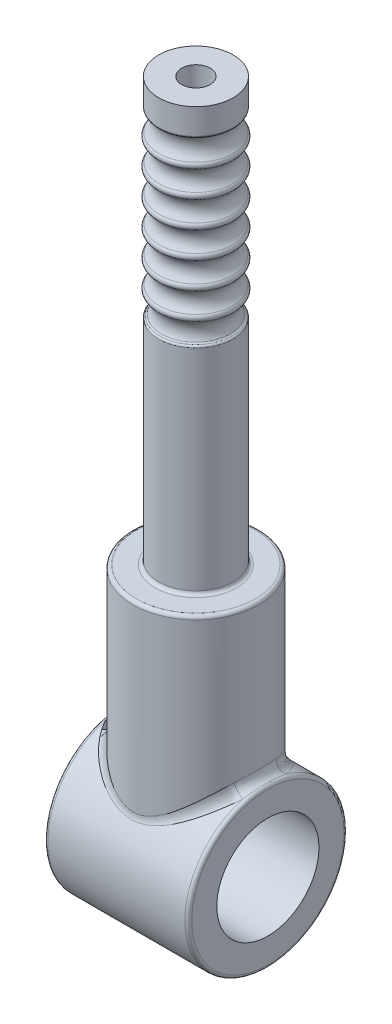
SolidWorks part; units mm, degrees
material "1060 Alloy"
ref_plane "Front Plane" through (0, 0, 0) normal (0, 0, 1) x (1, 0, 0)
ref_plane "Top Plane" through (0, 0, 0) normal (0, 1, 0) x (1, 0, 0)
ref_plane "Right Plane" through (0, 0, 0) normal (1, 0, 0) x (0, 0, -1)
sketch "Sketch1" plane through (0, 0, 0) normal (1, 0, 0) x (0, 0, -1)
  circle A0 centre (0, 0) radius 5.725
  circle A1 centre (0, 0) radius 3.675
  dimension "D1" = 11.45
  dimension "D2" = 7.35
extrude "Boss-Extrude1" add sketch "Sketch1" along normal mid plane 10.35
ref_plane "Plane1" through (0, -5.725, 0) normal (0, -1, 0) x (-1, 0, 0)
sketch "Sketch2" plane through (0, -5.725, 0) normal (0, 1, 0) x (1, 0, 0)
  circle A0 centre (0, 0) radius 4.53
  dimension "D1" = 9.06
extrude "Boss-Extrude2" add sketch "Sketch2" along normal blind 22.6
sketch "Sketch4" plane through (0, 16.875, 0) normal (0, 1, 0) x (1, 0, 0)
  circle A0 centre (0, 0) radius 2.675
  dimension "D1" = 5.35
extrude "Boss-Extrude3" add sketch "Sketch4" along normal blind 53 from surface starting at plane "Plane1"
sketch "Sketch3" plane through (5.175, 0, 0) normal (1, 0, 0) x (0, 0, -1)
  line L0 (4.53, -5.725) -> (4.53, -3.5007) construction
  line L1 (-4.53, -3.5007) -> (-4.53, -5.725) construction
  line L2 (0, -5.725) -> (4.53, -5.725) construction
  line L3 (4.53, -5.725) -> (4.53, -3.5007)
  line L4 (-4.53, -3.5007) -> (-4.53, -5.725)
  line L5 (-4.53, -5.725) -> (4.53, -5.725)
  circle A0 centre (0, 0) radius 3.675 construction
  circle A1 centre (0, 0) radius 5.725 construction
  arc A2 (-4.53, -3.5007) -> (4.53, -3.5007) centre (0, 0) ccw
  circle A3 centre (0, 0) radius 3.675
  circle M1 centre (0, 0) radius 5.725
  circle M2 centre (0, 0) radius 3.675
extrude "Cut-Extrude1" cut sketch "Sketch3" against normal through all contours L4 L5 M1 | L5 L3 M1 | M2 region at (5.175, -5.0878, -3.4462) region at (5.175, -5.0878, 3.4462) region at (5.175, 0, 0)
fillet "Fillet2" radius 0.25 2 edges at (-5.175, 0, -5.725) (5.175, 0, -5.725)
fillet "Fillet1" radius 0.7 1 edges at (-0.1545, 3.5041, 4.5274)
fillet "Fillet3" radius 0.25 2 edges at (0, 16.875, 2.675) (0, 16.875, 4.53)
ref_plane "Plane2" through (0, 45.275, 0) normal (0, 1, 0) x (1, 0, 0)
sketch "Sketch8" plane through (0, 45.275, 0) normal (0, 1, 0) x (1, 0, 0)
  circle A0 centre (0, 0) radius 2.675 construction
  circle A1 centre (0, 0) radius 2.675
extrude "Cut-Extrude2" cut sketch "Sketch8" against normal blind 12.88
sketch "Sketch9" plane through (0, 0, 0) normal (0, 0, 1) x (1, 0, 0)
  line L0 (0, 45.275) -> (0, 32.395)
  line L1 (-2.315, 42.635) -> (-2.315, 35.035) construction
  line L2 (-2.315, 35.035) -> (-2.315, 33.1565) construction
  line L3 (-2.675, 45.275) -> (2.675, 45.275) construction
  line L4 (2.675, 32.395) -> (-2.675, 32.395) construction
  line L5 (0, 32.395) -> (-2.75, 32.395)
  line L6 (-2.75, 32.395) -> (-2.75, 45.275) construction
  line L7 (-2.75, 45.275) -> (0, 45.275)
  line L8 (0, 38.835) -> (-2.75, 38.835) construction
  line L9 (-2.75, 43.585) -> (0, 43.585) construction
  line L10 (-2.75, 41.685) -> (0, 41.685) construction
  line L11 (-2.75, 39.785) -> (0, 39.785) construction
  line L12 (-2.75, 37.885) -> (0, 37.885) construction
  line L13 (-2.75, 35.985) -> (0, 35.985) construction
  line L14 (0, 34.085) -> (-2.75, 34.085) construction
  line L15 (-2.45, 43.585) -> (-2.45, 34.085) construction
  line L18 (-2.675, 32.395) -> (-2.675, 17.125) construction
  circle A0 centre (-2.45, 43.585) radius 0.3
  circle A1 centre (-2.45, 41.685) radius 0.3
  circle A2 centre (-2.45, 39.785) radius 0.3
  circle A3 centre (-2.45, 37.885) radius 0.3
  circle A4 centre (-2.45, 35.985) radius 0.3
  circle A5 centre (-2.45, 34.085) radius 0.3
  arc A6 (-2.6575, 43.8017) -> (-2.525, 45.275) centre (-3.4354, 44.6142) ccw
  arc A7 (-2.646, 43.3579) -> (-2.646, 41.9121) centre (-3.2699, 42.635) cw
  arc A8 (-2.646, 41.4579) -> (-2.646, 40.0121) centre (-3.2699, 40.735) cw
  arc A9 (-2.646, 39.5579) -> (-2.646, 38.1121) centre (-3.2699, 38.835) cw
  arc A10 (-2.646, 37.6579) -> (-2.646, 36.2121) centre (-3.2699, 36.935) cw
  arc A11 (-2.646, 35.7579) -> (-2.646, 34.3121) centre (-3.2699, 35.035) cw
  arc A12 (-2.6575, 33.8683) -> (-2.525, 32.395) centre (-3.4354, 33.0558) cw
  dimension "D1" = 2.75
  dimension "D2" = 0.6
  dimension "D4" = 1.9
  dimension "D5" = 0.15
  dimension "D3" = 2.315
revolve "Revolve1" add sketch "Sketch9" angle 360 about L0 region at (-1.1749, 38.835, 0) region at (-2.45, 43.585, 0) region at (-2.45, 34.085, 0) region at (-2.45, 41.685, 0) region at (-2.45, 35.985, 0) region at (-2.45, 39.785, 0) region at (-2.45, 37.885, 0)
fillet "Fillet5" radius 0.15 2 edges at (0, 45.275, 2.675) (0, 32.395, 2.675)
fillet "Fillet6" radius 0.2 2 edges at (0, 32.395, -2.525) (0, 45.275, -2.525)
hole_wizard "M2.5x0.45 Tapped Hole1" positions "Sketch7" profile "Sketch6" tap size "M2.5x0.45" standard "ANSI Metric"
sketch "Sketch7" plane through (0, 47.275, 0) normal (0, 1, 0) x (1, 0, 0)
  point P0 (0, 0)
cosmetic thread "Hole Thread1" parameters "D1"=5, "D2"=2.5
sketch "Sketch6" plane through (0, 47.275, 0) normal (1, 0, 0) x (0, 0, 1)
  line L0 (0, 0) -> (0, 7.8659)
  line L1 (0, 7.8659) -> (1.025, 7.25)
  line L2 (1.025, 7.25) -> (1.025, 0)
  line L5 (1.025, 0) -> (0, 0)
  line L10 (0, 7.8659) -> (-1.025, 7.25) construction
  line L11 (0, -6.35) -> (0, 107.95) construction
  dimension "Tap Drill Dia." = 2.05
  dimension "Tap Drill Depth" = 7.25
  dimension "Drill Angle" = 118
